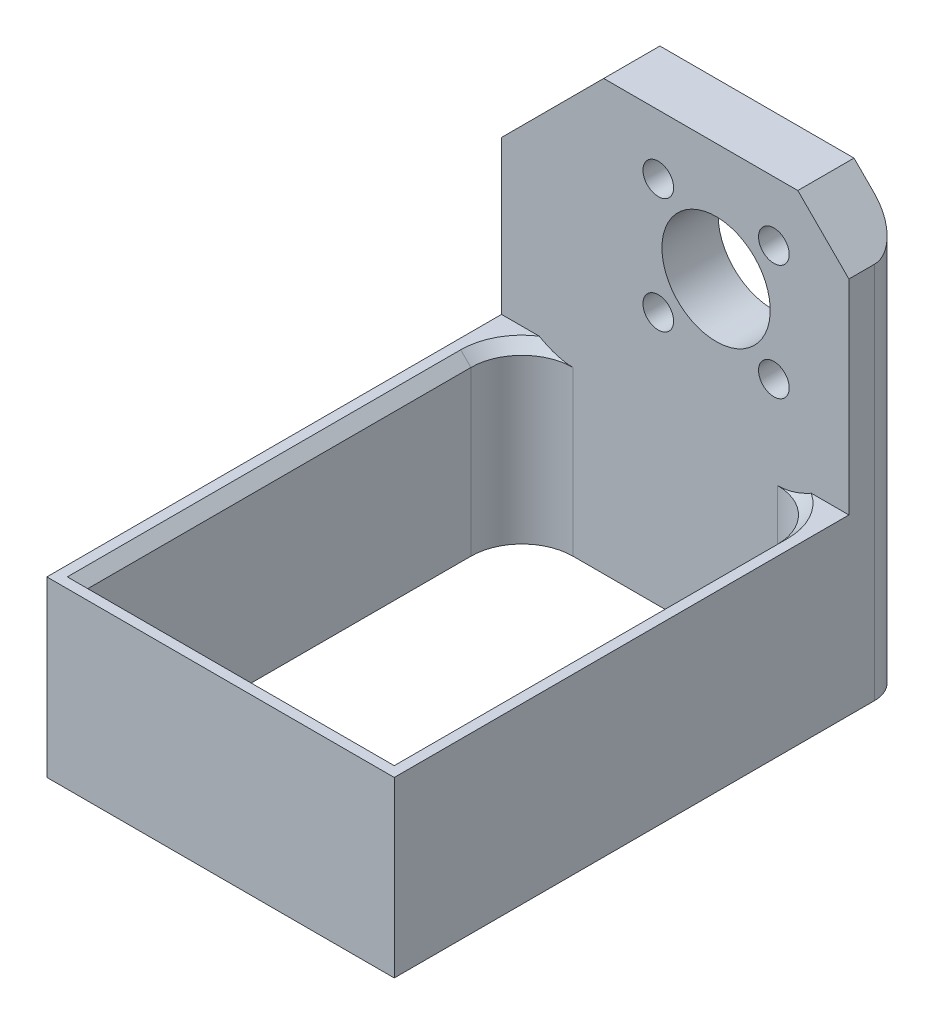
SolidWorks part; units mm, degrees
ref_plane "Płaszczyzna przednia" through (0, 0, 0) normal (0, 0, 1) x (1, 0, 0)
ref_plane "Płaszczyzna górna" through (0, 0, 0) normal (0, 1, 0) x (1, 0, 0)
ref_plane "Płaszczyzna prawa" through (0, 0, 0) normal (1, 0, 0) x (0, 0, -1)
sketch "Szkic1" plane through (0, 0, 0) normal (0, 1, 0) x (1, 0, 0)
  line L1 (-17, 25) -> (17, 25)
  line L2 (-17, 25) -> (-17, -25)
  line L3 (-17, -25) -> (17, -25)
  line L4 (17, 25) -> (17, -25)
  line L5 (-17, 25) -> (17, -25) construction
  line L6 (-17, -25) -> (17, 25) construction
  point P0 (0, 0)
  dimension "D1" = 34
  dimension "D2" = 50
extrude "Dodanie-wyciągnięcie1" add sketch "Szkic1" along normal blind 17
sketch "Szkic2" plane through (0, 17, 0) normal (0, 1, 0) x (1, 0, 0)
  line L0 (0, 25) -> (0, -25) construction
  line L1 (17, 25) -> (-17, 25) construction
  line L2 (-17, -25) -> (17, -25) construction
  line L3 (-17, 25) -> (-17, -25) construction
  line L4 (15, 7) -> (-15, 7)
  line L5 (15, 7) -> (15, -23)
  line L6 (15, -23) -> (-15, -23)
  line L7 (-15, 7) -> (-15, -23)
  line L8 (15, 7) -> (-15, -23) construction
  line L9 (15, -23) -> (-15, 7) construction
  point P6 (0, -8)
  dimension "D1" = 2
  dimension "D2" = 2
  dimension "D3" = 30
extrude "Wytnij-wyciągnięcie1" cut sketch "Szkic2" against normal blind 20
sketch "Szkic3" plane through (0, 17, 0) normal (0, 1, 0) x (1, 0, 0)
  line L0 (17, -25) -> (17, 25) construction
  line L1 (17, 25) -> (-17, 25)
  line L2 (17, 25) -> (17, 19.5)
  line L3 (17, 19.5) -> (-17, 19.5)
  line L4 (-17, 25) -> (-17, 19.5)
  line L5 (17, 25) -> (-17, 25) construction
  line L6 (-17, 25) -> (-17, -25) construction
  line L7 (-17, -25) -> (17, -25) construction
  dimension "D1" = 44.5
extrude "Dodanie-wyciągnięcie2" add sketch "Szkic3" along normal blind 25
sketch "Szkic4" plane through (0, 0, -25) normal (0, 0, -1) x (-1, 0, 0)
  line L1 (-4, 30.5) -> (-9.6569, 36.1569) construction
  line L2 (-4, 30.5) -> (-4, 38.5) construction
  line L3 (-17, 42) -> (17, 42) construction
  line L4 (0, 0) -> (0, 62.7345) construction
  line L6 (-17, 0) -> (17, 0) construction
  circle A0 centre (1.6569, 36.1569) radius 1.5
  circle A1 centre (-4, 30.5) radius 5.3
  circle A2 centre (-4, 30.5) radius 8
  circle A3 centre (-9.6569, 36.1569) radius 1.5
  circle A4 centre (-4, 30.5) radius 8
  circle A5 centre (1.6569, 24.8431) radius 1.5
  circle A6 centre (-4, 30.5) radius 8
  circle A7 centre (-9.6569, 24.8431) radius 1.5
  circle A8 centre (-4, 30.5) radius 8
  point P21 (-4, 30.5)
  dimension "D1" = 4
  dimension "D2" = 11.5
  dimension "D3" = 10.6
  dimension "D4" = 16
  dimension "D5" = 3
  dimension "D6" = 45
  dimension "D7" = 4
extrude "Wytnij-wyciągnięcie2" cut sketch "Szkic4" against normal blind 25 contours A2 A3 | A2 A3 | A2 A0 | A0 A2 | A6 A7 | A6 A7 | A4 A5 | A4 A5 | A1 region at (-2.0886, 36.5886, -25) region at (-1.1893, 35.6893, -25) region at (9.1893, 35.6893, -25) region at (10.0886, 36.5886, -25) region at (-2.0886, 24.4114, -25) region at (-1.1893, 25.3107, -25) region at (9.1893, 25.3107, -25) region at (10.0886, 24.4114, -25) region at (4, 30.5, -25)
chamfer "Sfazowanie1" distance 10 angle 45 1 edges at (-17, 42, -22.25)
chamfer "Sfazowanie2" distance 5 angle 45 1 edges at (17, 42, -22.25)
fillet "Zaokrąglenie1" radius 3 2 edges at (17, 18.5, -25) (-17, 16, -25)
sketch "Szkic5" plane through (0, 0, -7) normal (0, 0, 1) x (1, 0, 0)
  line L0 (15, 17) -> (-15, 17) construction
  line L1 (-15, 17) -> (15, 17)
  line L2 (-15, 17) -> (-15, 0)
  line L3 (-15, 0) -> (15, 0)
  line L4 (15, 17) -> (15, 0)
extrude "Wytnij-wyciągnięcie3" cut sketch "Szkic5" against normal up to surface (12.5 mm away) up to face at (-3.1569, 36.1569, -19.5)
fillet "Zaokrąglenie2" radius 5 2 edges at (15, 8.5, -19.5) (-15, 8.5, -19.5)
chamfer "Sfazowanie3" distance 1 angle 45 5 edges at (13.5355, 17, -18.0355) (-13.5355, 17, -18.0355) (15, 17, 4.25) (0, 17, 23) (-15, 17, 4.25)
